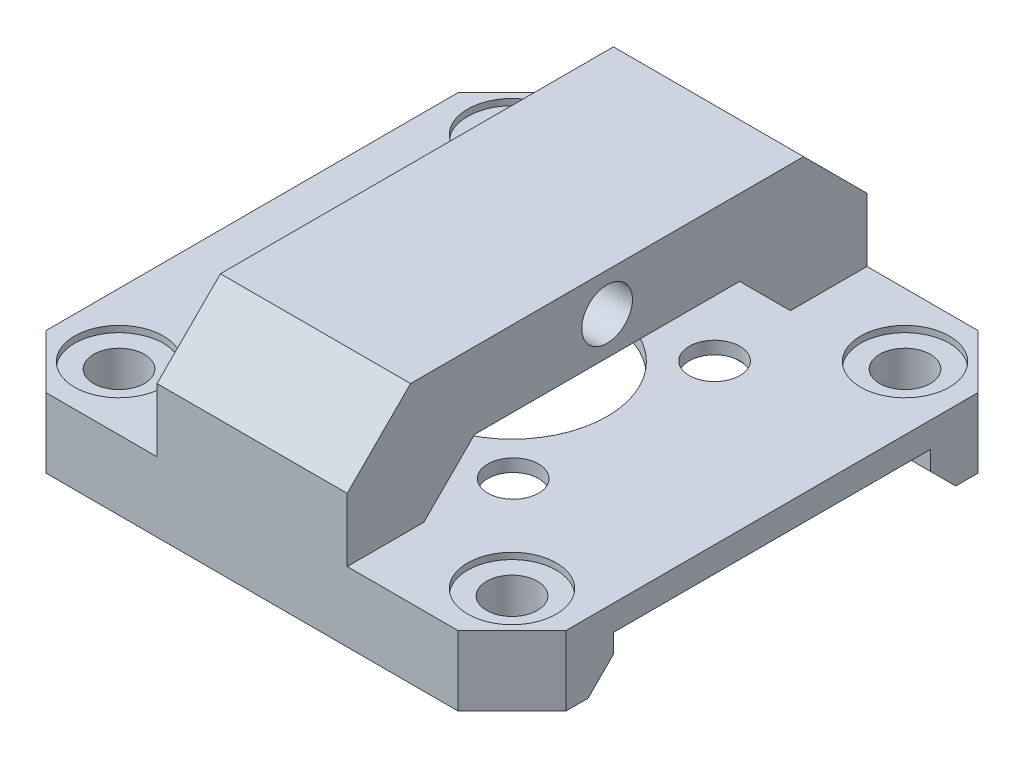
SolidWorks part; units mm, degrees
ref_plane "Front Plane" through (0, 0, 0) normal (0, 0, 1) x (1, 0, 0)
ref_plane "Top Plane" through (0, 0, 0) normal (0, 1, 0) x (1, 0, 0)
ref_plane "Right Plane" through (0, 0, 0) normal (1, 0, 0) x (0, 0, -1)
sketch "Sketch2" plane through (0, 0, 0) normal (0, 1, 0) x (1, 0, 0)
  line L1 (-20.5, -20.5) -> (20.5, -20.5)
  line L2 (-20.5, -20.5) -> (-20.5, 20.5)
  line L3 (-20.5, 20.5) -> (20.5, 20.5)
  line L4 (20.5, -20.5) -> (20.5, 20.5)
  line L5 (-20.5, -20.5) -> (20.5, 20.5) construction
  line L6 (-20.5, 20.5) -> (20.5, -20.5) construction
  point P0 (0, 0)
  dimension "D1" = 41
  dimension "D2" = 41
extrude "Boss-Extrude1" add sketch "Sketch2" along normal blind 2
sketch "Sketch3" plane through (0, 0, 0) normal (0, -1, 0) x (1, 0, 0)
  line L0 (-7.9432, -8.0372) -> (0, 0) construction
  line L5 (-7.9432, -8.0372) -> (7.9432, -8.0372) construction
  line L6 (-7.9432, -8.0372) -> (-7.9432, 8.0372) construction
  line L7 (-7.9432, 8.0372) -> (7.9432, 8.0372) construction
  line L8 (7.9432, -8.0372) -> (7.9432, 8.0372) construction
  line L9 (0, 0) -> (7.9432, 8.0372) construction
  line L10 (0, 0) -> (7.9432, -8.0372) construction
  line L11 (-7.9432, 8.0372) -> (0, 0) construction
  arc A1 (7.9432, 8.0372) -> (-7.9432, 8.0372) centre (0, 0) ccw construction
  arc A2 (-7.9432, -8.0372) -> (7.9432, -8.0372) centre (0, 0) ccw construction
  arc A3 (-7.9432, 8.0372) -> (-7.9432, -8.0372) centre (0, 0) ccw construction
  arc A4 (7.9432, -8.0372) -> (8.0686, 7.9112) centre (0, 0) ccw construction
  circle A5 centre (-7.9432, 8.0372) radius 2
  circle A10 centre (8.0372, 7.9432) radius 2
  circle A12 centre (7.9432, -8.0372) radius 2
  circle A13 centre (-8.0372, -7.9432) radius 2
  arc A14 (8.0686, 7.9112) -> (7.9432, 8.0372) centre (0, 0) ccw construction
  point P15 (-1.4144, -0.0142)
  point P19 (0, 0)
  dimension "D1" = 22.6
  dimension "D2" = 4
  dimension "D4" = 4
extrude "Cut-Extrude1" cut sketch "Sketch3" against normal through all
sketch "Sketch4" plane through (0, 2, 0) normal (0, 1, 0) x (1, 0, 0)
  circle A0 centre (0, 0) radius 7.5
  dimension "D1" = 15
extrude "Cut-Extrude2" cut sketch "Sketch4" against normal through all
sketch "Sketch5" plane through (0, 0, 0) normal (0, -1, 0) x (1, 0, 0)
  line L1 (-12.5, -12.5) -> (12.5, -12.5)
  line L2 (-12.5, -12.5) -> (-12.5, 12.5)
  line L3 (-12.5, 12.5) -> (12.5, 12.5)
  line L4 (12.5, -12.5) -> (12.5, 12.5)
  line L5 (-12.5, -12.5) -> (12.5, 12.5) construction
  line L6 (-12.5, 12.5) -> (12.5, -12.5) construction
  point P0 (0, 0)
  dimension "D1" = 25
  dimension "D2" = 25
extrude "Cut-Extrude3" cut sketch "Sketch5" against normal blind 1
sketch "Sketch6" plane through (0, 2, 0) normal (0, 1, 0) x (1, 0, 0)
  line L0 (-20.5, 16.2574) -> (-16.2574, 20.5)
  line L1 (-20.5, 20.5) -> (-20.5, -20.5) construction
  line L2 (20.5, 20.5) -> (-20.5, 20.5) construction
  line L4 (16.2574, 20.5) -> (20.5, 16.2574)
  line L5 (20.5, -20.5) -> (20.5, 20.5) construction
  line L7 (20.5, -16.2574) -> (16.2574, -20.5)
  line L8 (-20.5, -20.5) -> (20.5, -20.5) construction
  line L10 (-16.2574, -20.5) -> (-20.5, -16.2574)
  line L12 (-2.4898, 0) -> (5.6129, 0) construction
  line L13 (0, 5.0948) -> (0, 0) construction
  line L14 (0, 0) -> (3.8649, 3.8649) construction
  line L15 (-20.5, -16.2574) -> (-20.5, -20.5)
  line L16 (-20.5, -20.5) -> (-16.2574, -20.5)
  line L17 (16.2574, -20.5) -> (20.5, -20.5)
  line L18 (20.5, -20.5) -> (20.5, -16.2574)
  line L19 (20.5, 16.2574) -> (20.5, 20.5)
  line L20 (20.5, 20.5) -> (16.2574, 20.5)
  line L21 (-16.2574, 20.5) -> (-20.5, 20.5)
  line L22 (-20.5, 20.5) -> (-20.5, 16.2574)
  dimension "D1" = 6
  dimension "D2" = 6
  dimension "D3" = 45
  dimension "D4" = 6
  dimension "D5" = 6
extrude "Cut-Extrude4" cut sketch "Sketch6" against normal through all
sketch "Sketch7" plane through (0, 0, 0) normal (0, -1, 0) x (1, 0, 0)
  line L0 (-15.5, 15.5) -> (0, 0) construction
  line L1 (-15.5, -15.5) -> (15.5, -15.5) construction
  line L2 (-15.5, -15.5) -> (-15.5, 15.5) construction
  line L3 (-15.5, 15.5) -> (15.5, 15.5) construction
  line L4 (15.5, -15.5) -> (15.5, 15.5) construction
  line L5 (-15.5, -15.5) -> (0, 0) construction
  line L6 (0, 0) -> (15.5, -15.5) construction
  line L7 (0, 0) -> (15.5, 15.5) construction
  arc A0 (-15.5, -15.5) -> (15.5, -15.5) centre (0, 0) ccw construction
  arc A1 (-15.5, 15.5) -> (-15.5, -15.5) centre (0, 0) ccw construction
  arc A2 (15.5, -15.5) -> (15.5, 15.5) centre (0, 0) ccw construction
  arc A3 (15.5, 15.5) -> (-15.5, 15.5) centre (0, 0) ccw construction
  circle A4 centre (-15.5, 15.5) radius 2
  circle A5 centre (15.5, 15.5) radius 2
  circle A6 centre (15.5, -15.5) radius 2
  circle A7 centre (-15.5, -15.5) radius 2
  point P16 (0, 0)
  dimension "D2" = 4
  dimension "D4" = 31
  dimension "D3" = 4
extrude "Cut-Extrude5" cut sketch "Sketch7" against normal through all
sketch "Sketch8" plane through (0, 0, 0) normal (0, -1, 0) x (1, 0, 0)
  line L0 (-12.5, -12.5) -> (-12.5, 12.5) construction
  line L1 (-12.5, -12.5) -> (-20.477, -12.5) construction
  line L2 (-12.5, 12.5) -> (-20.477, 12.5) construction
  line L3 (-20.477, -12.5) -> (-20.477, 12.5) construction
  line L4 (12.5, -12.5) -> (12.5, 12.5) construction
  line L5 (12.5, -12.5) -> (20.4876, -12.5) construction
  line L6 (12.5, 12.5) -> (20.4876, 12.5) construction
  line L7 (20.4876, -12.5) -> (20.4876, 12.5) construction
  line L8 (-12.5, 12.5) -> (12.5, 12.5)
  line L9 (-12.5, 12.5) -> (-12.5, 20.5)
  line L10 (12.5, 12.5) -> (12.5, 20.5)
  line L11 (-12.5, 20.5) -> (12.5, 20.5)
  line L12 (12.5, -12.5) -> (-12.5, -12.5)
  line L13 (12.5, -12.5) -> (12.5, -20.4578)
  line L14 (-12.5, -12.5) -> (-12.5, -20.4578)
  line L15 (12.5, -20.4578) -> (-12.5, -20.4578)
  line L16 (-16.2574, 20.5) -> (16.2574, 20.5) construction
extrude "Boss-Extrude2" add sketch "Sketch8" along normal blind 3.5
sketch "Sketch9" plane through (0, -3.5, 0) normal (0, -1, 0) x (1, 0, 0)
  circle A0 centre (0, 16.5) radius 2
  circle A1 centre (0, -16.4789) radius 2
  dimension "D1" = 4
extrude "Cut-Extrude6" cut sketch "Sketch9" against normal through all
sketch "Sketch10" plane through (0, 0, 0) normal (0, -1, 0) x (1, 0, 0)
  line L0 (-20.5, -16.2574) -> (-16.2574, -20.5)
  line L1 (20.5, 12.5) -> (12.5, 12.5)
  line L2 (20.5, 12.5) -> (20.5, 16.2574)
  line L3 (16.2574, 20.5) -> (12.5, 20.5)
  line L4 (-20.5, 12.5) -> (-20.5, 16.2574)
  line L5 (-20.5, -12.5) -> (-12.5, -12.5)
  line L6 (-20.5, -12.5) -> (-20.5, -16.2574)
  line L8 (20.5, -12.5) -> (20.5, -16.2574)
  line L9 (-20.5, 16.2574) -> (-16.2574, 20.5)
  line L10 (16.2574, 20.5) -> (20.5, 16.2574)
  line L11 (20.5, -16.2574) -> (16.2574, -20.5)
  line L12 (-20.5, -12.5) -> (-20.5, -16.2574)
  line L13 (-12.5, 12.5) -> (-20.5, 12.5)
  line L14 (-12.5, 20.5) -> (-16.2574, 20.5)
  line L15 (12.5, -12.5) -> (20.5, -12.5)
  line L16 (-12.5, -12.5) -> (-12.5, 12.5)
  line L17 (-12.5, 12.5) -> (-12.5, 20.5)
  line L18 (-12.5, 20.5) -> (-16.2574, 20.5)
  line L19 (-16.2574, 20.5) -> (-20.5, 16.2574)
  line L20 (-20.5, 16.2574) -> (-20.5, -16.2574)
  line L21 (-20.5, -16.2574) -> (-16.2574, -20.5)
  line L22 (-16.2574, -20.5) -> (16.2574, -20.5)
  line L23 (16.2574, -20.5) -> (20.5, -16.2574)
  line L24 (20.5, -16.2574) -> (20.5, 16.2574)
  line L25 (20.5, 16.2574) -> (16.2574, 20.5)
  line L26 (16.2574, 20.5) -> (12.5, 20.5)
  line L27 (12.5, 20.5) -> (12.5, 12.5)
  line L28 (12.5, 12.5) -> (12.5, -12.5)
  line L29 (12.5, -12.5) -> (12.5, -20.4578)
  line L30 (12.5, -20.4578) -> (-12.5, -20.4578)
  line L31 (-12.5, -20.4578) -> (-12.5, -12.5)
  line L33 (-12.5, 12.5) -> (-12.5, 20.5)
  line L34 (-12.5, 20.5) -> (-16.2574, 20.5)
  line L35 (-16.2574, 20.5) -> (-20.5, 16.2574)
  line L36 (-20.5, 16.2574) -> (-20.5, 12.5)
  line L37 (-20.5, -16.2574) -> (-16.2574, -20.5)
  line L39 (16.2574, -20.5) -> (20.5, -16.2574)
  line L40 (20.5, -16.2574) -> (20.5, 16.2574)
  line L41 (20.5, 16.2574) -> (16.2574, 20.5)
  line L42 (16.2574, 20.5) -> (12.5, 20.5)
  line L43 (12.5, 20.5) -> (12.5, 12.5)
  line L44 (12.5, 12.5) -> (12.5, -12.5)
  line L45 (12.5, -12.5) -> (12.5, -20.4578)
  line L47 (-12.5, -20.4578) -> (-12.5, -12.5)
  line L50 (12.5, 20.5) -> (-12.5, 20.5) construction
  circle A0 centre (-15.5, 15.5) radius 2
  circle A1 centre (15.5, 15.5) radius 2
  circle A2 centre (15.5, -15.5) radius 2
  circle A3 centre (-15.5, -15.5) radius 2
  circle M19 centre (-15.5, -15.5) radius 2
  circle M20 centre (15.5, -15.5) radius 2
  circle M21 centre (15.5, 15.5) radius 2
  circle M22 centre (-15.5, 15.5) radius 2
  line M24 (-12.5, 12.5) -> (-12.5, 20.5)
  line M25 (-12.5, 20.5) -> (-16.2574, 20.5)
  line M26 (-16.2574, 20.5) -> (-20.5, 16.2574)
  line M27 (-20.5, 16.2574) -> (-20.5, -16.2574)
  line M28 (-20.5, -16.2574) -> (-16.2574, -20.5)
  line M29 (-16.2574, -20.5) -> (16.2574, -20.5)
  line M30 (16.2574, -20.5) -> (20.5, -16.2574)
  line M31 (20.5, -16.2574) -> (20.5, 16.2574)
  line M32 (20.5, 16.2574) -> (16.2574, 20.5)
  line M33 (16.2574, 20.5) -> (12.5, 20.5)
  line M34 (12.5, 20.5) -> (12.5, 12.5)
  line M36 (12.5, -12.5) -> (12.5, -20.4578)
  line M37 (12.5, -20.4578) -> (-12.5, -20.4578)
  line M38 (-12.5, -20.4578) -> (-12.5, -12.5)
  dimension "D1" = 0
extrude "Boss-Extrude3" add sketch "Sketch10" along normal up to surface (3.5 mm away) contours L13 M24 M25 M26 M27 M22 | L1 M31 M32 M33 M34 M21 | L15 L5 M36 M37 M38 M27 M28 M29 M30 M31 M19 M20 region at (-20.0823, 0, -14.3787) region at (-20.3869, 0, 14.3787) region at (16.5, 0, 12.6131) up to face at (0, -3.5, 14.5)
sketch "Sketch11" plane through (0, 2, 0) normal (0, 1, 0) x (1, 0, 0)
  circle A0 centre (-15.5, 15.5) radius 3.5
  circle A1 centre (15.5, 15.5) radius 3.5
  circle A2 centre (15.5, -15.5) radius 3.5
  circle A3 centre (-15.5, -15.5) radius 3.5
  point P12 (0, 0)
  dimension "D1" = 7
  dimension "D2" = 4
extrude "Cut-Extrude7" cut sketch "Sketch11" against normal offset from surface (3.5 mm away) 2 up to face at (0, -3.5, -18.4789)
sketch "Sketch12" plane through (0, 0, 0) normal (0, -1, 0) x (1, 0, 0)
  line L0 (-12.5, 12.5) -> (-12.5, -12.5) construction
  line L1 (-20.5, -12.5) -> (-12.5, -12.5)
  line L2 (-20.5, -12.5) -> (-20.5, -10.5)
  line L3 (-20.5, -10.5) -> (-12.5, -10.5)
  line L4 (-12.5, -12.5) -> (-12.5, -10.5)
  line L5 (-25.9518, 0) -> (26.3784, 0) construction
  line L6 (0, 23.4974) -> (0, -23.7021) construction
  line L7 (-12.5, 12.5) -> (-12.5, 10.5)
  line L8 (-20.5, 12.5) -> (-12.5, 12.5)
  line L9 (-20.5, 12.5) -> (-20.5, 10.5)
  line L10 (-20.5, 10.5) -> (-12.5, 10.5)
  line L11 (12.5, -12.5) -> (12.5, -10.5)
  line L12 (20.5, -10.5) -> (12.5, -10.5)
  line L13 (20.5, -12.5) -> (20.5, -10.5)
  line L14 (20.5, -12.5) -> (12.5, -12.5)
  line L15 (20.5, 10.5) -> (12.5, 10.5)
  line L16 (20.5, 12.5) -> (20.5, 10.5)
  line L17 (20.5, 12.5) -> (12.5, 12.5)
  line L18 (12.5, 12.5) -> (12.5, 10.5)
  dimension "D1" = 2
extrude "Boss-Extrude4" add sketch "Sketch12" along normal up to surface (3.5 mm away) up to face at (0, -3.5, 14.5)
sketch "Sketch13" plane through (0, 2, 0) normal (0, 1, 0) x (1, 0, 0)
  circle A0 centre (-15.5, 15.5) radius 3.5
  circle A1 centre (15.5, 15.5) radius 3.5
  circle A2 centre (15.5, -15.5) radius 3.5
  circle A3 centre (-15.5, -15.5) radius 3.5
  point P12 (0, 0)
  dimension "D1" = 4
extrude "Cut-Extrude8" cut sketch "Sketch13" against normal up to surface (3.5 mm away) up to face at (-15.5, -1.5, -13.5)
sketch "Sketch14" plane through (0, -1.5, 0) normal (0, 1, 0) x (1, 0, 0)
  circle A0 centre (-15.5, -15.5) radius 2
  circle A1 centre (-15.5, -15.5) radius 3.5
  circle A2 centre (-15.5, 15.5) radius 3.5
  circle A3 centre (-15.5, 15.5) radius 2
  circle A4 centre (15.5, 15.5) radius 3.5
  circle A5 centre (15.5, 15.5) radius 2
  circle A6 centre (15.5, -15.5) radius 3.5
  circle A7 centre (15.5, -15.5) radius 2
  point P16 (0, 0)
  dimension "D1" = 4
extrude "Boss-Extrude5" add sketch "Sketch14" along normal offset from surface (3 mm away) 0.5 up to face at (-15.5, 2, 19)
sketch "Sketch15" plane through (0, 2, 0) normal (0, 1, 0) x (1, 0, 0)
  line L0 (0, 20.5) -> (0, -20.5) construction
  line L1 (16.2574, 20.5) -> (-16.2574, 20.5) construction
  line L2 (-16.2574, -20.5) -> (16.2574, -20.5) construction
  line L3 (0, -16.5) -> (7.5, -16.5) construction
  line L4 (0, -16.5) -> (-7.5, -16.5) construction
  line L5 (0, 16.4789) -> (7.5, 16.4789) construction
  line L6 (0, 16.4789) -> (-7.5, 16.4789) construction
  line L7 (-7.5, 20.5) -> (-7.5, 16.4789) construction
  line L8 (-7.5, 16.4789) -> (-7.5, 12.4578) construction
  line L9 (-7.5, -20.5) -> (-7.5, -16.5) construction
  line L10 (-7.5, -16.5) -> (-7.5, -12.5) construction
  line L11 (-3.025, 0) -> (3.025, 0) construction
  line L12 (7.5, 12.4578) -> (-7.5, 12.4578)
  line L13 (7.5, 12.4578) -> (7.5, 20.5)
  line L14 (7.5, 20.5) -> (-7.5, 20.5)
  line L15 (-7.5, 12.4578) -> (-7.5, 20.5)
  line L16 (7.5, -12.5) -> (-7.5, -12.5)
  line L17 (7.5, -12.5) -> (7.5, -20.5)
  line L18 (7.5, -20.5) -> (-7.5, -20.5)
  line L19 (-7.5, -12.5) -> (-7.5, -20.5)
  circle A0 centre (0, 16.4789) radius 2
  circle A1 centre (0, -16.4789) radius 2
  point P27 (0, 0)
  dimension "D1" = 7.5
extrude "Boss-Extrude6" add sketch "Sketch15" along normal blind 4
sketch "Sketch16" plane through (0, -3.5, 0) normal (0, -1, 0) x (1, 0, 0)
  line L0 (-20.5, 10.5) -> (-20.5, 16.2574) construction
  line L1 (-12.5, -12.5) -> (-20.5, -12.5)
  line L2 (-12.5, -12.5) -> (-12.5, 12.5)
  line L3 (-12.5, 12.5) -> (-20.5, 12.5)
  line L4 (-20.5, -12.5) -> (-20.5, 12.5)
  line L5 (12.5, 12.5) -> (20.5, 12.5)
  line L6 (12.5, 12.5) -> (12.5, -12.5)
  line L7 (20.5, 12.5) -> (20.5, -12.5)
  line L8 (12.5, -12.5) -> (20.5, -12.5)
  line L9 (20.5, 16.2574) -> (20.5, 10.5) construction
extrude "Cut-Extrude9" cut sketch "Sketch16" against normal up to surface (3.5 mm away) up to face at (16.5, 0, 0)
chamfer "Chamfer3" distance 2 angle 45 2 edges at (0, -3.5, -12.5) (0, -3.5, 12.5)
chamfer "Chamfer4" distance 2 angle 45 2 edges at (12.5, 0, 0) (-12.5, 0, 0)
sketch "Sketch17" plane through (0, 6, 0) normal (0, 1, 0) x (1, 0, 0)
  circle A0 centre (0, 16.4789) radius 2
  circle A1 centre (0, -16.4789) radius 2
extrude "Boss-Extrude7" add sketch "Sketch17" against normal through all
sketch "Sketch21" plane through (0, 6, 0) normal (0, 1, 0) x (1, 0, 0)
  line L0 (7.5, 12.4578) -> (7.5, 20.5) construction
  line L1 (-7.5, -15.4578) -> (7.5, -15.4578)
  line L2 (-7.5, -15.4578) -> (-7.5, 15.4578)
  line L3 (-7.5, 15.4578) -> (7.5, 15.4578)
  line L4 (7.5, -15.4578) -> (7.5, 15.4578)
  line L5 (-7.5, -15.4578) -> (7.5, 15.4578) construction
  line L6 (-7.5, 15.4578) -> (7.5, -15.4578) construction
  line L7 (-7.5, 12.4578) -> (7.5, 12.4578) construction
  point P0 (0, 0)
  dimension "D1" = 3
extrude "Cut-Extrude11" cut sketch "Sketch21" against normal up to surface (4 mm away) up to face at (0, 2, 0.0053)
sketch "Sketch18" plane through (0, 6, 0) normal (0, 1, 0) x (1, 0, 0)
  line L1 (-7.5, -20.5) -> (7.5, -20.5)
  line L3 (-7.5, 20.5) -> (7.5, 20.5)
  line L4 (7.5, -20.5) -> (7.5, 20.5)
  line L5 (-7.5, -20.5) -> (7.5, 20.5) construction
  line L6 (-7.5, 20.5) -> (7.5, -20.5) construction
  line L7 (-7.5, 20.5) -> (-7.5, -20.5)
  point P0 (0, 0)
extrude "Boss-Extrude8" add sketch "Sketch18" along normal blind 6
chamfer "Chamfer5" distance 5 angle 45 4 edges at (0, 12, -20.5) (0, 12, 20.5) (0, 6, 15.4578) (0, 6, -15.4578)
sketch "Sketch22" plane through (7.5, 0, 0) normal (1, 0, 0) x (0, 0, -1)
  line L0 (0, 6) -> (0, 12) construction
  line L2 (-10.4578, 6) -> (10.4578, 6) construction
  line L3 (-15.5, 12) -> (15.5, 12) construction
  circle A0 centre (0, 9) radius 2
  dimension "D1" = 4
extrude "Cut-Extrude12" cut sketch "Sketch22" against normal blind 4
mirror "Mirror1" about plane through (0, 0, 0) normal (1, 0, 0) of "Cut-Extrude12"
